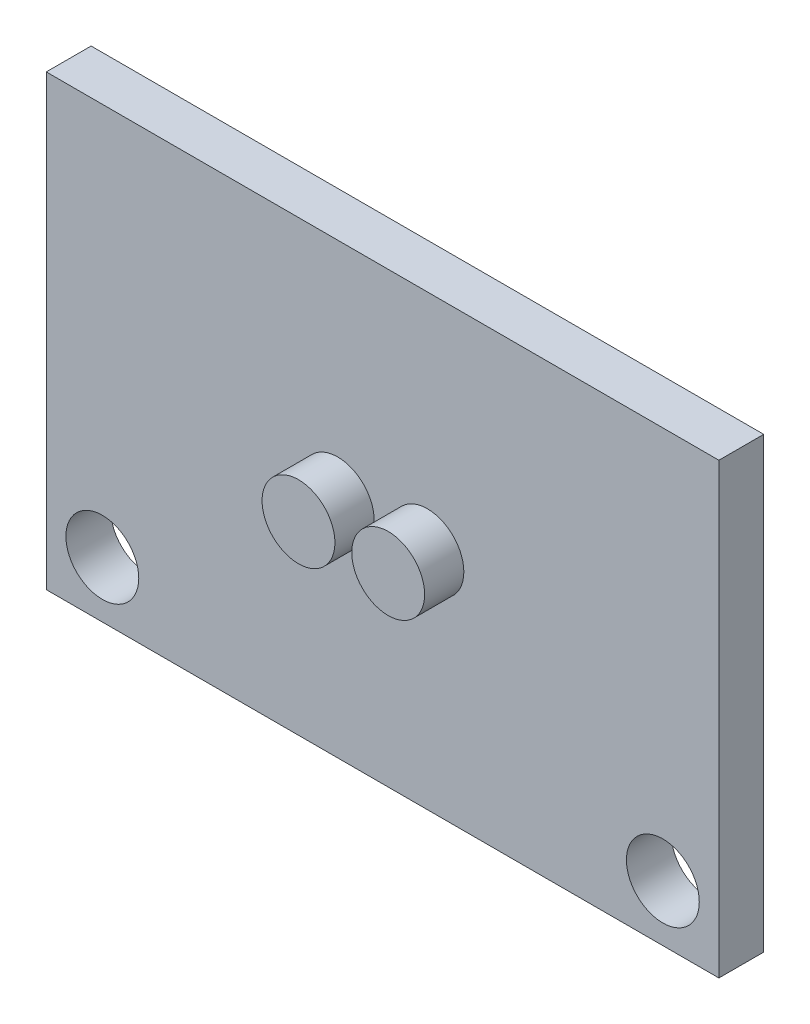
SolidWorks part; units mm, degrees
ref_plane "前视基准面" through (0, 0, 0) normal (0, 0, 1) x (1, 0, 0)
ref_plane "上视基准面" through (0, 0, 0) normal (0, 1, 0) x (1, 0, 0)
ref_plane "右视基准面" through (0, 0, 0) normal (1, 0, 0) x (0, 0, -1)
other "Configuration Table"
sketch "草图1" plane through (0, 0, 0) normal (0, 0, 1) x (1, 0, 0)
  line L1 (-12, 80) -> (12, 80)
  line L2 (-12, 80) -> (-12, 96)
  line L3 (-12, 96) -> (12, 96)
  line L4 (12, 80) -> (12, 96)
extrude "VL53L1X_carrier_PROVISIONAL" [suppressed] add sketch "草图1" along normal blind 1.6 from offset 0
sketch "草图2" plane through (0, 0, 0) normal (0, 0, 1) x (1, 0, 0)
  circle A0 centre (-3, 88) radius 2
  circle A1 centre (3, 88) radius 2
extrude "TOF_optics_reference" [suppressed] add sketch "草图2" along normal blind 1 from offset -1 separate body
sketch "草图3" plane through (0, 0, 0) normal (0, 0, 1) x (1, 0, 0)
  line L1 (-12, 80) -> (12, 80)
  line L2 (-12, 80) -> (-12, 96)
  line L3 (-12, 96) -> (12, 96)
  line L4 (12, 80) -> (12, 96)
extrude "V10_TOF_candidate_carrier24x16" add sketch "草图3" along normal blind 1.6 from offset 0
sketch "草图4" plane through (0, 0, 0) normal (0, 0, 1) x (1, 0, 0)
  circle A0 centre (-1.6, 88) radius 1.3
  circle A1 centre (1.6, 88) radius 1.3
extrude "V10_TOF_optical_packages_facing_front" add sketch "草图4" along normal blind 1.4 from offset 1.6
sketch "草图5" plane through (0, 0, 1.6) normal (0, 0, 1) x (1, 0, 0)
  circle A0 centre (-10, 82) radius 1.3
  circle A1 centre (10, 82) radius 1.3
extrude "V10_TOF_two_candidate_holes20mm" cut sketch "草图5" against normal blind 1.6
